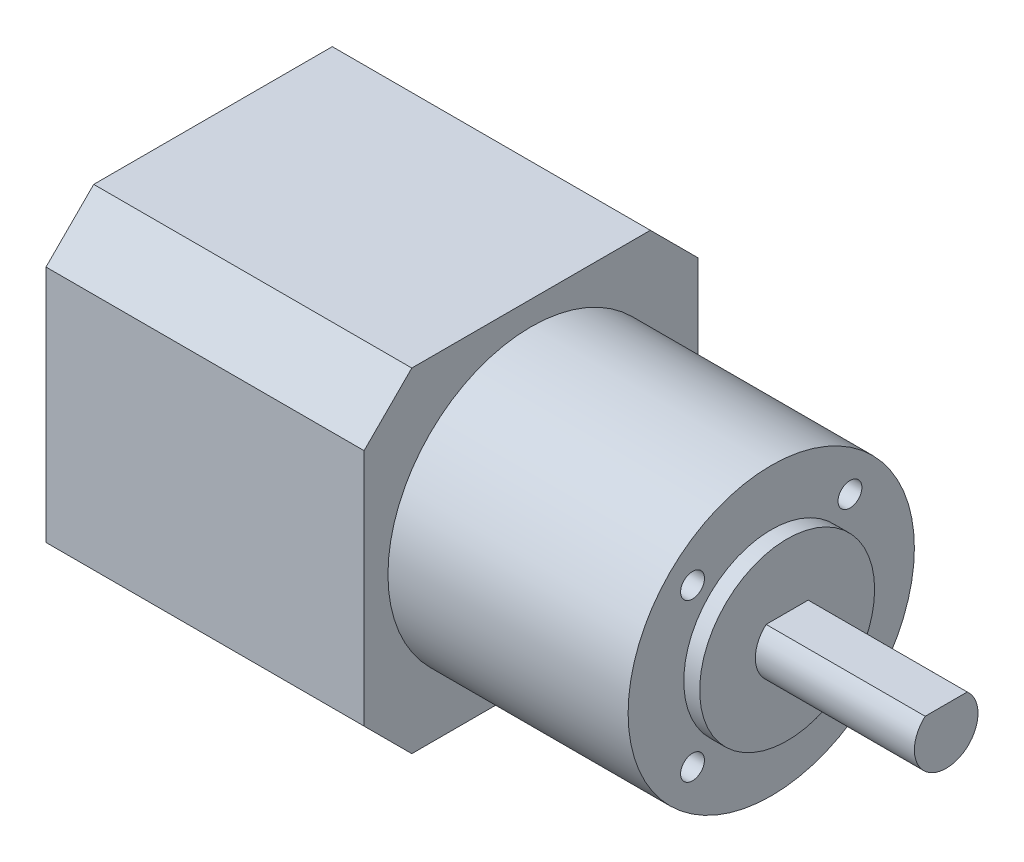
SolidWorks part; units mm, degrees
ref_plane "Front Plane" through (0, 0, 0) normal (0, 0, 1) x (1, 0, 0)
ref_plane "Top Plane" through (0, 0, 0) normal (0, 1, 0) x (1, 0, 0)
ref_plane "Right Plane" through (0, 0, 0) normal (1, 0, 0) x (0, 0, -1)
sketch "Sketch1" plane through (0, 0, 0) normal (1, 0, 0) x (0, 0, -1)
  line L0 (-21, 15) -> (-15, 21)
  line L1 (-15, -21) -> (15, -21)
  line L2 (-21, -15) -> (-21, 15)
  line L3 (-15, 21) -> (15, 21)
  line L4 (21, -15) -> (21, 15)
  line L5 (-21, -21) -> (21, 21) construction
  line L6 (-21, 21) -> (21, -21) construction
  line L7 (15, 21) -> (21, 15)
  line L8 (15, -21) -> (21, -15)
  line L9 (-21, -15) -> (-15, -21)
  point P0 (0, 0)
  dimension "D1" = 42
  dimension "D12" = 6
  dimension "D13" = 6
  dimension "D14" = 6
  dimension "D15" = 6
  dimension "D2" = 42
extrude "Boss-Extrude1" add sketch "Sketch1" along normal blind 40
sketch "Sketch2" plane through (40, 0, 0) normal (1, 0, 0) x (0, 0, -1)
  line L0 (0, 0) -> (24.4009, -24.4009) construction
  line L3 (-15, 21) -> (-21, 15) construction
  circle A0 centre (0, 0) radius 18
  circle A1 centre (0, 0) radius 14 construction
  circle A2 centre (-9.8995, 9.8995) radius 1.5
  circle A3 centre (9.8995, 9.8995) radius 1.5
  circle A4 centre (9.8995, -9.8995) radius 1.5
  circle A5 centre (-9.8995, -9.8995) radius 1.5
  point P13 (-18, 18)
  dimension "D1" = 36
  dimension "D2" = 28
  dimension "D3" = 3
  dimension "D4" = 4
extrude "Boss-Extrude2" add sketch "Sketch2" along normal blind 30.2
sketch "Sketch3" plane through (70.2, 0, 0) normal (1, 0, 0) x (0, 0, -1)
  circle A0 centre (0, 0) radius 11
  dimension "D1" = 22
extrude "Boss-Extrude3" add sketch "Sketch3" along normal blind 2
sketch "Sketch4" plane through (72.2, 0, 0) normal (1, 0, 0) x (0, 0, -1)
  line L0 (2.6458, 3) -> (-2.6458, 3)
  arc A0 (-2.6458, 3) -> (2.6458, 3) centre (0, 0) ccw
  point P5 (-2.4784, 3)
  point P6 (-1.0973, 3)
  dimension "D1" = 8
  dimension "D2" = 3
extrude "Boss-Extrude4" add sketch "Sketch4" along normal blind 20
